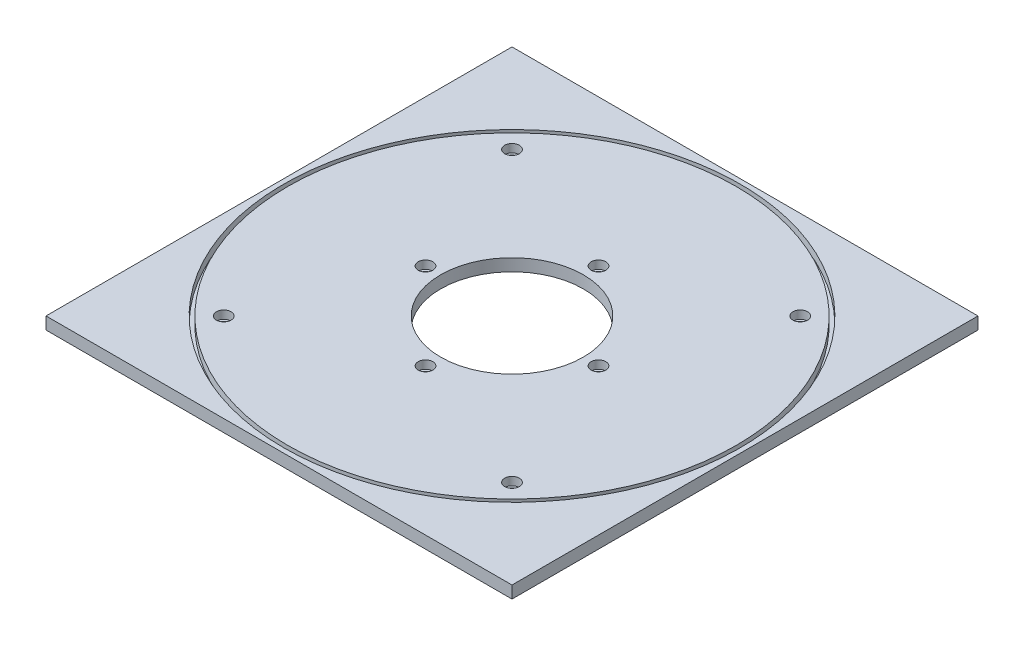
SolidWorks part; units mm, degrees
ref_plane "Front Plane" through (0, 0, 0) normal (0, 0, 1) x (1, 0, 0)
ref_plane "Top Plane" through (0, 0, 0) normal (0, 1, 0) x (1, 0, 0)
ref_plane "Right Plane" through (0, 0, 0) normal (1, 0, 0) x (0, 0, -1)
sketch "Sketch1" plane through (0, 0, 0) normal (0, 1, 0) x (1, 0, 0)
  line L0 (-285.75, -285.75) -> (-285.75, 285.75)
  line L1 (-285.75, -285.75) -> (285.75, -285.75)
  line L2 (-285.75, 285.75) -> (285.75, 285.75)
  line L3 (285.75, -285.75) -> (285.75, 285.75)
  line L4 (-285.75, -285.75) -> (285.75, 285.75) construction
  line L5 (-285.75, 285.75) -> (285.75, -285.75) construction
  point P0 (0, 0)
  point P2 (0, 0)
  dimension "D1" = 571.5
extrude "plate" add sketch "Sketch1" along normal blind 15
sketch "Sketch2" plane through (0, 15, 0) normal (0, 1, 0) x (1, 0, 0)
  circle A0 centre (0, 0) radius 87.5
  dimension "D1" = 175
extrude "bearing-hole" cut sketch "Sketch2" against normal through all
sketch "Sketch4" plane through (0, 15, 0) normal (0, 1, 0) x (1, 0, 0)
  circle A0 centre (0, 0) radius 280
  circle A1 centre (0, 0) radius 275
  point P0 (0, 0)
  point P6 (0, 0)
  dimension "D1" = 560
  dimension "D2" = 550
extrude "Cut-Extrude3" cut sketch "Sketch4" against normal blind 10
hole_wizard "CBORE for M10 SHCS" positions "Sketch5" profile "Sketch6" counterbore size "M10" standard "ANSI Metric" end condition through all
sketch "Sketch5" plane through (0, 15, 0) normal (0, 1, 0) x (1, 0, 0)
  line L1 (106.066, 0) -> (0, -106.066) construction
  line L2 (106.066, 0) -> (0, 106.066) construction
  line L3 (0, 106.066) -> (-106.066, 0) construction
  line L4 (0, -106.066) -> (-106.066, 0) construction
  line L5 (106.066, 0) -> (-106.066, 0) construction
  line L6 (0, 106.066) -> (0, -106.066) construction
  line L7 (-176.7767, 176.7767) -> (176.7767, 176.7767) construction
  line L8 (-176.7767, 176.7767) -> (-176.7767, -176.7767) construction
  line L9 (176.7767, 176.7767) -> (176.7767, -176.7767) construction
  line L10 (-176.7767, -176.7767) -> (176.7767, -176.7767) construction
  line L11 (-176.7767, 176.7767) -> (176.7767, -176.7767) construction
  line L12 (176.7767, 176.7767) -> (-176.7767, -176.7767) construction
  point P36 (0, 0)
  point P198 (-106.066, 0)
  point P201 (0, 106.066)
  point P204 (106.066, 0)
  point P207 (0, -106.066)
  point P210 (0, 0)
  point P341 (176.7767, 176.7767)
  point P344 (-176.7767, 176.7767)
  point P347 (176.7767, -176.7767)
  point P350 (-176.7767, -176.7767)
sketch "Sketch6" plane through (0, 15, 0) normal (1, 0, 0) x (0, 0, 1)
  line L0 (0, 0) -> (0, 15)
  line L1 (0, 15) -> (6, 15)
  line L2 (6, 15) -> (6, 10)
  line L3 (6, 10) -> (9, 10)
  line L4 (9, 10) -> (9, 0)
  line L5 (9, 0) -> (0, 0)
  line L6 (0, -6.35) -> (0, 107.95) construction
  dimension "Thru Hole Dia." = 12
  dimension "Thru Hole Depth" = 15
  dimension "C'Bore Dia." = 18
  dimension "C'Bore Depth" = 10
